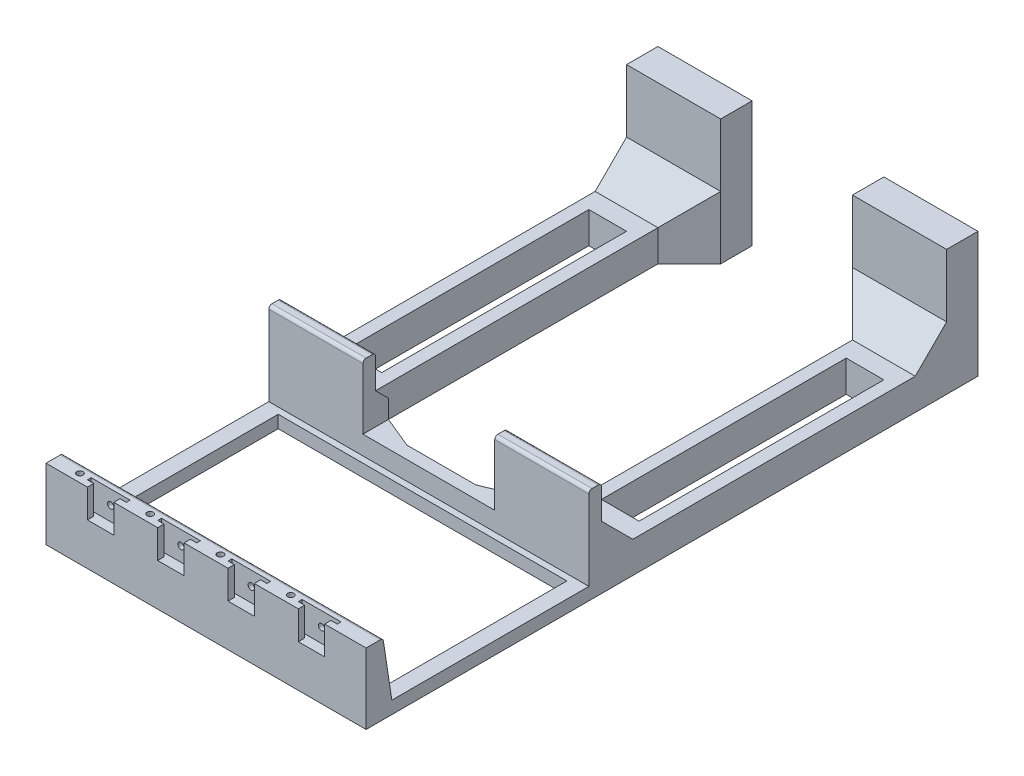
SolidWorks part; units mm, degrees
ref_plane "前视基准面" through (0, 0, 0) normal (0, 0, 1) x (1, 0, 0)
ref_plane "上视基准面" through (0, 0, 0) normal (0, 1, 0) x (1, 0, 0)
ref_plane "右视基准面" through (0, 0, 0) normal (1, 0, 0) x (0, 0, -1)
other "Configuration Table"
sketch "草图1" plane through (0, 0, 0) normal (0, 1, 0) x (1, 0, 0)
  line L1 (0, 0) -> (-102, 0)
  line L2 (0, 0) -> (0, 75)
  line L3 (0, 75) -> (-102, 75)
  line L4 (-102, 0) -> (-102, 75)
  dimension "D1" = 102
  dimension "D2" = 75
extrude "凸台-拉伸1" add sketch "草图1" along normal blind 22.5
sketch "草图2" plane through (0, 22.5, 0) normal (0, 1, 0) x (1, 0, 0)
  line L0 (-102, 75) -> (-102, 0) construction
  line L1 (-90.8, 2) -> (-88.8, 2)
  line L2 (-90.8, 2) -> (-90.8, 3.2)
  line L3 (-90.8, 3.2) -> (-78.4, 3.2)
  line L4 (-78.4, 2) -> (-78.4, 3.2)
  line L5 (-68.4, 2) -> (-66.4, 2)
  line L6 (-68.4, 2) -> (-68.4, 3.2)
  line L7 (-68.4, 3.2) -> (-56, 3.2)
  line L8 (-56, 2) -> (-56, 3.2)
  line L9 (-46, 3.2) -> (-33.6, 3.2)
  line L10 (-46, 3.2) -> (-46, 2)
  line L11 (-46, 2) -> (-44, 2)
  line L12 (-33.6, 3.2) -> (-33.6, 2)
  line L13 (-23.6, 3.2) -> (-11.2, 3.2)
  line L14 (-23.6, 3.2) -> (-23.6, 2)
  line L15 (-23.6, 2) -> (-21.6, 2)
  line L16 (-11.2, 3.2) -> (-11.2, 2)
  line L19 (-102, 0) -> (0, 0) construction
  line L20 (-13.2, 2) -> (-11.2, 2)
  line L22 (-88.8, 2) -> (-88.8, 0)
  line L23 (-88.8, 0) -> (-80.4, 0)
  line L24 (-80.4, 2) -> (-80.4, 0)
  line L26 (-66.4, 2) -> (-66.4, 0)
  line L27 (-66.4, 0) -> (-58, 0)
  line L28 (-58, 2) -> (-58, 0)
  line L30 (-44, 2) -> (-44, 0)
  line L31 (-44, 0) -> (-35.6, 0)
  line L32 (-35.6, 2) -> (-35.6, 0)
  line L34 (-21.6, 2) -> (-21.6, 0)
  line L35 (-21.6, 0) -> (-13.2, 0)
  line L36 (-13.2, 2) -> (-13.2, 0)
  line L37 (-35.6, 2) -> (-33.6, 2)
  line L38 (-58, 2) -> (-56, 2)
  line L39 (-80.4, 2) -> (-78.4, 2)
  point P16 (-68.4, 2.6)
  dimension "D1" = 12.4
  dimension "D2" = 12.4
  dimension "D3" = 12.4
  dimension "D4" = 12.4
  dimension "D5" = 10
  dimension "D6" = 10
  dimension "D7" = 10
  dimension "D8" = 11.2
  dimension "D9" = 2
  dimension "D10" = 2
  dimension "D11" = 2
  dimension "D12" = 2
  dimension "D13" = 1.2
  dimension "D14" = 1.2
  dimension "D15" = 1.2
  dimension "D16" = 1.2
  dimension "D17" = 2
  dimension "D18" = 2
  dimension "D19" = 2
  dimension "D20" = 2
  dimension "D21" = 2
  dimension "D22" = 2
  dimension "D23" = 2
  dimension "D24" = 2
extrude "切除-拉伸1" cut sketch "草图2" against normal offset from surface (9.06 mm away) 13.44 up to face at (-51, 0, -37.5)
sketch "草图3" plane through (0, 22.5, 0) normal (0, 1, 0) x (1, 0, 0)
  line L0 (0, 0) -> (0, 75) construction
  line L1 (-102, 75) -> (0, 75)
  line L2 (-102, 75) -> (-102, 8.2)
  line L3 (-102, 8.2) -> (0, 8.2)
  line L4 (0, 75) -> (0, 8.2)
  line L5 (-11.2, 3.2) -> (-23.6, 3.2) construction
  dimension "D1" = 5
extrude "切除-拉伸2" cut sketch "草图3" against normal blind 12
sketch "草图4" plane through (-102, 0, 0) normal (-1, 0, 0) x (0, 0, 1)
  line L6 (-75, 10.5) -> (-8.2, 10.5) construction
  line L7 (-71, 10.5) -> (-8.2, 10.5)
  line L8 (-71, 10.5) -> (-71, 4)
  line L9 (-71, 4) -> (-8.2, 4)
  line L10 (-8.2, 10.5) -> (-8.2, 4)
  line L11 (-75, 10.5) -> (-75, 0) construction
  line L12 (-75, 0) -> (0, 0) construction
  line L13 (-8.2, 10.5) -> (-8.2, 22.5) construction
  dimension "D1" = 4
  dimension "D2" = 4
extrude "切除-拉伸3" cut sketch "草图4" against normal through all
sketch "草图6" plane through (0, 10.5, 0) normal (0, 1, 0) x (1, 0, 0)
  line L4 (-102, 71) -> (0, 71)
  line L5 (0, 71) -> (0, 75)
  line L6 (0, 75) -> (-102, 75)
  line L7 (-102, 75) -> (-102, 71)
  line L8 (-102, 71) -> (0, 71)
  line L9 (0, 71) -> (0, 75)
  line L10 (0, 75) -> (-102, 75)
  line L11 (-102, 75) -> (-102, 71)
  dimension "D1" = 0
extrude "凸台-拉伸2" add sketch "草图6" along normal blind 20
sketch "草图7" plane through (0, 4, 0) normal (0, 1, 0) x (1, 0, 0)
  line L0 (0, 71) -> (0, 8.2) construction
  line L1 (-97, 69) -> (-5, 69)
  line L2 (-97, 69) -> (-97, 10.2)
  line L3 (-97, 10.2) -> (-5, 10.2)
  line L4 (-5, 69) -> (-5, 10.2)
  line L5 (-102, 71) -> (-102, 8.2) construction
  line L6 (-102, 71) -> (0, 71) construction
  line L7 (0, 8.2) -> (-102, 8.2) construction
  dimension "D1" = 5
  dimension "D2" = 5
  dimension "D3" = 2
  dimension "D4" = 2
extrude "切除-拉伸5" cut sketch "草图7" against normal blind 8
sketch "草图9" plane through (-102, 0, 0) normal (-1, 0, 0) x (0, 0, 1)
  line L0 (-8.2, 22.5) -> (-5.4, 22.5)
  line L2 (-5.4, 22.5) -> (-8.2, 4)
  line L3 (-8.2, 4) -> (-8.2, 22.5)
  dimension "D1" = 2.8
extrude "切除-拉伸6" cut sketch "草图9" against normal blind 108
fillet "圆角2" radius 1 3 edges at (-51, 30.5, -75) (-51, 30.5, -71) (-51, 22.5, -5.4)
sketch "草图10" plane through (0, 0, -3.2) normal (0, 0, 1) x (1, 0, 0)
  line L0 (-88.8, 22.5) -> (-80.4, 13.44) construction
  line L1 (-80.4, 22.5) -> (-88.8, 13.44) construction
  line L2 (-66.4, 22.5) -> (-58, 13.44) construction
  line L3 (-51, 0) -> (-51, 38.7871) construction
  line L4 (-58, 22.5) -> (-66.4, 13.44) construction
  line L5 (-102, 0) -> (0, 0) construction
  circle A0 centre (-84.6, 17.97) radius 1
  circle A1 centre (-62.2, 17.97) radius 1
  circle A2 centre (-39.8, 17.97) radius 1
  circle A3 centre (-17.4, 17.97) radius 1
  dimension "D1" = 2
  dimension "D2" = 2
extrude "切除-拉伸7" cut sketch "草图10" against normal blind 10
sketch "草图14" plane through (0, 22.5, 0) normal (0, 1, 0) x (1, 0, 0)
  line L0 (-23.6, 2) -> (-21.6, 2) construction
  line L1 (-23.6, 2) -> (-23.6, 3.2) construction
  line L2 (-46, 2) -> (-46, 3.2) construction
  line L3 (-68.4, 3.2) -> (-68.4, 2) construction
  line L4 (-90.8, 3.2) -> (-90.8, 2) construction
  circle A0 centre (-93.8, 2.6) radius 1
  circle A1 centre (-71.4, 2.6) radius 1
  circle A2 centre (-49, 2.6) radius 1
  circle A3 centre (-26.6, 2.6) radius 1
  dimension "D1" = 2
  dimension "D2" = 0.6
  dimension "D3" = 3
  dimension "D4" = 3
  dimension "D5" = 2
  dimension "D6" = 3
  dimension "D7" = 2
  dimension "D8" = 3
  dimension "D9" = 2
extrude "切除-拉伸8" cut sketch "草图14" against normal blind 10
sketch "草图15" plane through (0, 0, -75) normal (0, 0, -1) x (-1, 0, 0)
  line L1 (0, 0) -> (20, 0)
  line L2 (0, 0) -> (0, 10)
  line L3 (0, 10) -> (20, 10)
  line L4 (20, 0) -> (20, 10)
  line L5 (102, 0) -> (82, 0)
  line L6 (102, 0) -> (102, 10)
  line L7 (102, 10) -> (82, 10)
  line L8 (82, 0) -> (82, 10)
  dimension "D1" = 20
  dimension "D2" = 10
  dimension "D3" = 20
  dimension "D4" = 10
extrude "凸台-拉伸3" add sketch "草图15" along normal blind 120
sketch "草图16" plane through (-82, 0, 0) normal (1, 0, 0) x (0, 0, -1)
  line L1 (195, 10) -> (185, 10)
  line L2 (195, 10) -> (195, 0)
  line L3 (195, 0) -> (185, 0)
  line L4 (185, 10) -> (185, 0)
  dimension "D1" = 10
extrude "凸台-拉伸4" add sketch "草图16" along normal blind 80
chamfer "倒角1" distance 10 angle 45 4 edges at (-82, 5, -75) (-20, 5, -75) (-20, 5, -185) (-82, 5, -185)
sketch "草图17" plane through (0, 10, 0) normal (0, 1, 0) x (1, 0, 0)
  line L0 (0, 195) -> (0, 75) construction
  line L1 (-102, 195) -> (0, 195)
  line L2 (-102, 195) -> (-102, 185)
  line L3 (-102, 185) -> (0, 185)
  line L4 (0, 195) -> (0, 185)
extrude "凸台-拉伸5" add sketch "草图17" along normal blind 30
sketch "草图19" plane through (0, 40, 0) normal (0, 1, 0) x (1, 0, 0)
  line L0 (0, 71) -> (-102, 71) construction
  line L2 (-72, 185) -> (-72, 75)
  line L4 (-30, 185) -> (-30, 75)
  line L6 (-72, 75) -> (-72, 71)
  line L7 (-72, 71) -> (-30, 71)
  line L8 (-30, 75) -> (-30, 71)
  line L9 (0, 195) -> (-102, 195) construction
  line L11 (-72, 185) -> (-72, 195)
  line L12 (-72, 195) -> (-30, 195)
  line L13 (-30, 185) -> (-30, 195)
extrude "切除-拉伸9" cut sketch "草图19" against normal blind 50
sketch "草图20" plane through (0, 10, 0) normal (0, 1, 0) x (1, 0, 0)
  line L0 (-102, 185) -> (-102, 75) construction
  line L1 (-98, 169) -> (-86, 169)
  line L2 (-98, 169) -> (-98, 91)
  line L3 (-98, 91) -> (-86, 91)
  line L4 (-86, 169) -> (-86, 91)
  line L5 (-82, 175) -> (-82, 85) construction
  line L7 (-51, 71) -> (-51, 119.5555) construction
  line L8 (-30, 71) -> (-72, 71) construction
  line L9 (-4, 91) -> (-16, 91)
  line L10 (-16, 169) -> (-16, 91)
  line L11 (-4, 169) -> (-16, 169)
  line L12 (-4, 169) -> (-4, 91)
  dimension "D1" = 4
  dimension "D2" = 4
  dimension "D3" = 6
  dimension "D4" = 6
extrude "切除-拉伸10" cut sketch "草图20" against normal blind 50
sketch "草图21" plane through (-72, 0, 0) normal (1, 0, 0) x (0, 0, -1)
  line L1 (75, 10) -> (71, 10)
  line L2 (75, 10) -> (75, 0)
  line L3 (75, 0) -> (71, 0)
  line L4 (71, 10) -> (71, 0)
extrude "凸台-拉伸6" add sketch "草图21" along normal blind 50
chamfer "倒角2" distance 10 2 edges at (-72, 5, -75) (-30, 5, -75)
chamfer "倒角3" distance 10 angle 45 2 edges at (-15, 10, -185) (-87, 10, -75)
